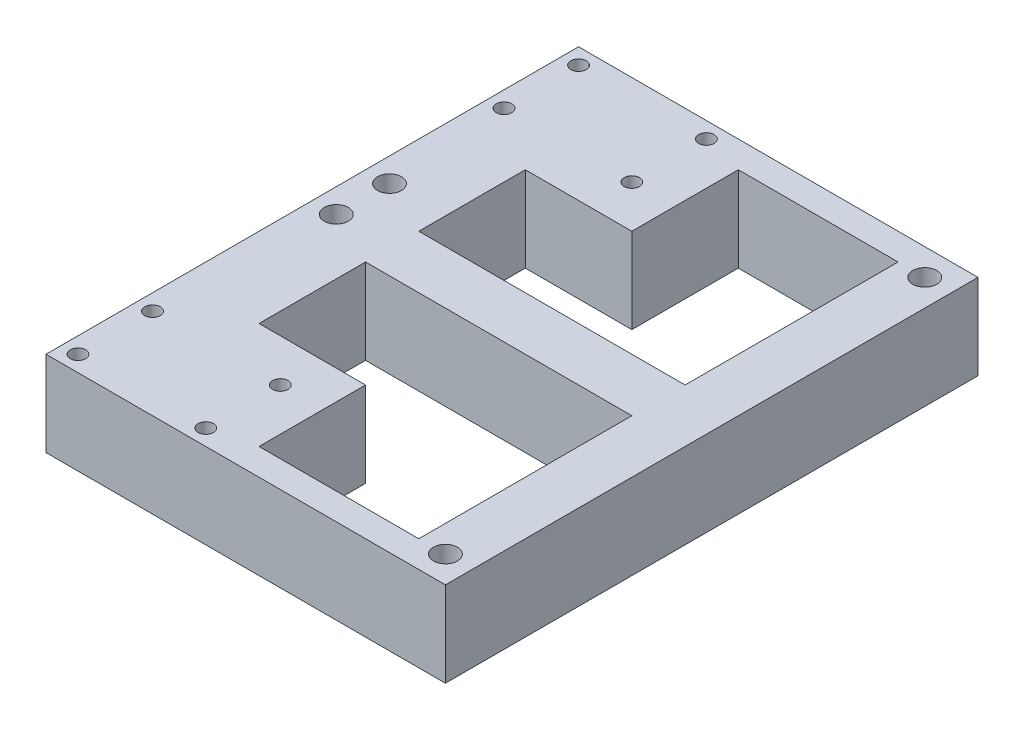
SolidWorks part; units mm, degrees
ref_plane "前视基准面" through (0, 0, 0) normal (0, 0, 1) x (1, 0, 0)
ref_plane "上视基准面" through (0, 0, 0) normal (0, 1, 0) x (1, 0, 0)
ref_plane "右视基准面" through (0, 0, 0) normal (1, 0, 0) x (0, 0, -1)
other "Configuration Table"
sketch "草图1" plane through (0, 0, 0) normal (0, 1, 0) x (1, 0, 0)
  line L1 (0, 0) -> (-75, 0)
  line L2 (0, 0) -> (0, 100)
  line L3 (0, 100) -> (-75, 100)
  line L4 (-75, 0) -> (-75, 100)
  dimension "D1" = 100
  dimension "D2" = 75
extrude "凸台-拉伸1" add sketch "草图1" along normal blind 16
sketch "草图6" plane through (0, 16, 0) normal (0, 1, 0) x (1, 0, 0)
  line L0 (-75, 100) -> (-75, 0) construction
  line L1 (-40, 45) -> (-5, 45)
  line L2 (-40, 25) -> (-40, 5)
  line L3 (-40, 5) -> (-5, 5)
  line L4 (-5, 45) -> (-5, 5)
  line L5 (0, 0) -> (0, 100) construction
  line L6 (-75, 0) -> (0, 0) construction
  line L7 (-75, 50) -> (-60.5255, 50) construction
  line L8 (-40, 95) -> (-5, 95)
  line L9 (-5, 55) -> (-5, 95)
  line L10 (-40, 55) -> (-5, 55)
  line L11 (-40, 75) -> (-40, 95)
  line L12 (-40, 75) -> (-70, 75)
  line L13 (-40, 45) -> (-70, 45)
  line L15 (-40, 25) -> (-70, 25)
  line L16 (-70, 45) -> (-70, 25)
  line L17 (-40, 55) -> (-70, 55)
  line L18 (-70, 55) -> (-70, 75)
  dimension "D1" = 35
  dimension "D2" = 5
  dimension "D3" = 5
  dimension "D4" = 40
  dimension "D5" = 30
  dimension "D6" = 20
extrude "切除-拉伸5" cut sketch "草图6" against normal up to next
sketch "草图8" plane through (0, 16, 0) normal (0, 1, 0) x (1, 0, 0)
  line L0 (-75, 100) -> (-72, 100) construction
  line L1 (0, 100) -> (-75, 100) construction
  line L2 (-72, 100) -> (-72, 97) construction
  line L3 (-72, 97) -> (-48, 97) construction
  line L4 (-48, 97) -> (-48, 83) construction
  line L5 (-48, 83) -> (-72, 83) construction
  line L6 (-75, 50) -> (-51.1245, 50) construction
  line L7 (-75, 100) -> (-75, 0) construction
  line L8 (-48, 17) -> (-72, 17) construction
  line L9 (-48, 3) -> (-48, 17) construction
  line L10 (-72, 3) -> (-48, 3) construction
  line L11 (-72, 0) -> (-72, 3) construction
  line L12 (-75, 0) -> (-72, 0) construction
  circle A0 centre (-72, 97) radius 1.45
  circle A1 centre (-72, 83) radius 1.45
  circle A2 centre (-48, 97) radius 1.45
  circle A3 centre (-48, 83) radius 1.45
  circle A4 centre (-48, 17) radius 1.45
  circle A5 centre (-48, 3) radius 1.45
  circle A6 centre (-72, 17) radius 1.45
  circle A7 centre (-72, 3) radius 1.45
  dimension "D6" = 2.9
  dimension "D7" = 2.9
  dimension "D8" = 2.9
  dimension "D9" = 2.9
  dimension "D1" = 3
  dimension "D2" = 3
  dimension "D3" = 24
  dimension "D4" = 14
  dimension "D5" = 24
extrude "切除-拉伸7" cut sketch "草图8" against normal through all
sketch "草图9" plane through (-5, 0, 0) normal (-1, 0, 0) x (0, 0, 1)
  line L0 (-45, 0) -> (-5, 0) construction
  line L1 (-5, 0) -> (-5, 16) construction
  line L2 (-5, 16) -> (-45, 16) construction
  line L3 (-45, 16) -> (-45, 0) construction
  line L4 (-95, 0) -> (-55, 0) construction
  line L5 (-55, 0) -> (-55, 16) construction
  line L6 (-55, 16) -> (-95, 16) construction
  line L7 (-95, 16) -> (-95, 0) construction
  line L8 (-45, 0) -> (-5, 0)
  line L9 (-5, 0) -> (-5, 16)
  line L10 (-5, 16) -> (-45, 16)
  line L11 (-45, 16) -> (-45, 0)
  line L12 (-95, 0) -> (-55, 0)
  line L13 (-55, 0) -> (-55, 16)
  line L14 (-55, 16) -> (-95, 16)
  line L15 (-95, 16) -> (-95, 0)
extrude "凸台-拉伸2" add sketch "草图9" along normal blind 5
sketch "草图10" plane through (0, 16, 0) normal (0, 1, 0) x (1, 0, 0)
  line L0 (0, 100) -> (0, 95) construction
  line L1 (0, 0) -> (0, 100) construction
  line L2 (0, 95) -> (-5, 95) construction
  line L3 (0, 50) -> (-16.1785, 50) construction
  circle A0 centre (-5, 95) radius 2.25
  circle A1 centre (-5, 5) radius 2.25
  dimension "D3" = 4.5
  dimension "D1" = 5
  dimension "D2" = 5
extrude "切除-拉伸8" cut sketch "草图10" against normal blind 5
sketch "草图11" plane through (0, 0, 0) normal (0, -1, 0) x (1, 0, 0)
  circle A0 centre (-5, -95) radius 2.25 construction
  circle A1 centre (-5, -5) radius 2.25 construction
  circle A2 centre (-5, -95) radius 2.25
  circle A3 centre (-5, -5) radius 2.25
extrude "切除-拉伸9" cut sketch "草图11" against normal blind 5
sketch "草图12" plane through (-70, 0, 0) normal (1, 0, 0) x (0, 0, -1)
  line L0 (25, 0) -> (45, 0) construction
  line L1 (45, 0) -> (45, 16) construction
  line L2 (45, 16) -> (25, 16) construction
  line L3 (25, 16) -> (25, 0) construction
  line L4 (55, 0) -> (75, 0) construction
  line L5 (75, 0) -> (75, 16) construction
  line L6 (75, 16) -> (55, 16) construction
  line L7 (55, 16) -> (55, 0) construction
  line L8 (25, 0) -> (45, 0)
  line L9 (45, 0) -> (45, 16)
  line L10 (45, 16) -> (25, 16)
  line L11 (25, 16) -> (25, 0)
  line L12 (55, 0) -> (75, 0)
  line L13 (75, 0) -> (75, 16)
  line L14 (75, 16) -> (55, 16)
  line L15 (55, 16) -> (55, 0)
extrude "凸台-拉伸3" add sketch "草图12" along normal blind 10
sketch "草图13" plane through (0, 16, 0) normal (0, 1, 0) x (1, 0, 0)
  line L0 (-75, 50) -> (-70.5, 50) construction
  line L1 (-75, 100) -> (-75, 0) construction
  line L3 (-70.5, 50) -> (-70.5, 60) construction
  circle A0 centre (-70.5, 50) radius 2.25
  circle A1 centre (-70.5, 60) radius 2.25
  dimension "D4" = 4.5
  dimension "D5" = 4.5
  dimension "D3" = 10
  dimension "D1" = 4.5
  dimension "D2" = 10
extrude "切除-拉伸10" cut sketch "草图13" against normal blind 5
